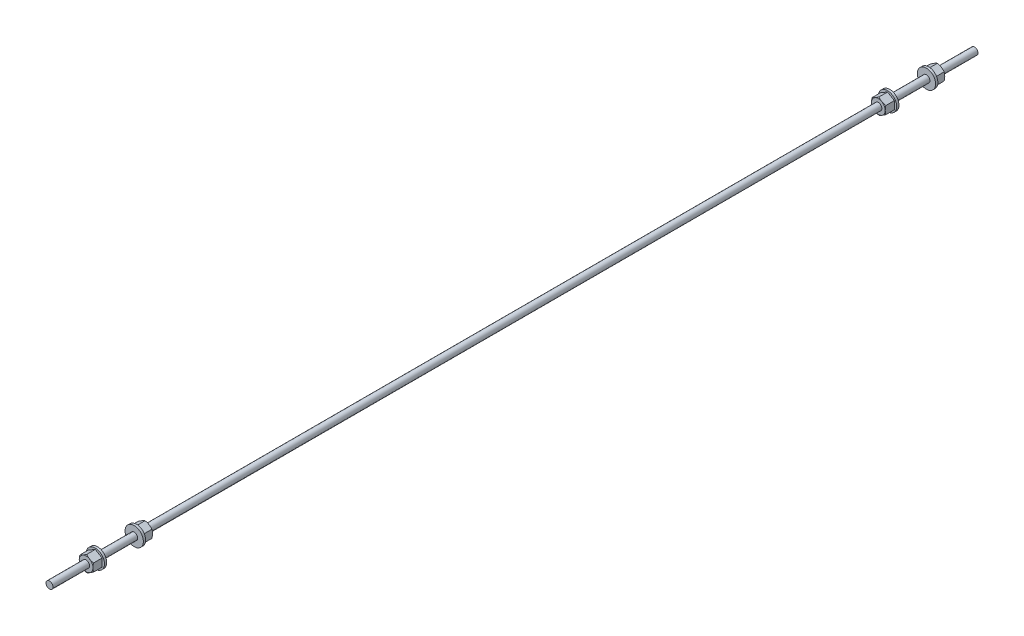
SolidWorks part; units mm, degrees
material "AISI 304"
ref_plane "Front Plane" through (0, 0, 0) normal (0, 0, 1) x (1, 0, 0)
ref_plane "Top Plane" through (0, 0, 0) normal (0, 1, 0) x (1, 0, 0)
ref_plane "Right Plane" through (0, 0, 0) normal (1, 0, 0) x (0, 0, -1)
sketch "Sketch1" plane through (0, 0, 0) normal (0, 0, 1) x (1, 0, 0)
  line L1 (0, 5.4993) -> (-4.7625, 2.7496)
  line L2 (-4.7625, 2.7496) -> (-4.7625, -2.7496)
  line L3 (-4.7625, -2.7496) -> (0, -5.4993)
  line L4 (0, -5.4993) -> (4.7625, -2.7496)
  line L5 (4.7625, -2.7496) -> (4.7625, 2.7496)
  line L6 (4.7625, 2.7496) -> (0, 5.4993)
  circle A0 centre (0, 0) radius 4.7625 construction
  dimension "Hex" = 9.525
extrude "Extrude1" add sketch "Sketch1" against normal blind 7.9375
sketch "Sketch13" plane through (0, 0, -7.9375) normal (0, 0, -1) x (-1, 0, 0)
  circle A0 centre (0, 0) radius 6.35
  dimension "Flange od" = 12.7
extrude "Extrude3" add sketch "Sketch13" against normal blind 1.5875
sketch "Sketch2" plane through (0, 0, 0) normal (0, 0, 1) x (1, 0, 0)
  circle A0 centre (0, 0) radius 4.7625 construction
  circle A1 centre (0, 0) radius 4.7625
extrude "Cut-Extrude1" cut sketch "Sketch2" against normal through all draft 60 flip side to cut
sketch "Sketch4" plane through (0, 0, 0) normal (0, 0, 1) x (1, 0, 0)
  circle A0 centre (0, 0) radius 2.413
  dimension "Thread Dia" = 4.826
sketch "Sketch14" plane through (0, 0, -7.9375) normal (0, 0, -1) x (-1, 0, 0)
  circle A0 centre (0, 0) radius 2.413
extrude "Boss-Extrude1" add sketch "Sketch14" along normal blind 12.7
ref_plane "Plane1" through (0, 0, -20.6375) normal (0, 0, -1) x (-1, 0, 0)
mirror "Mirror1" about plane through (0, 0, -20.6375) normal (0, 0, -1) of "Extrude3", "Cut-Extrude1", "Extrude1", "Boss-Extrude1"
sketch "Sketch15" plane through (0, 0, -41.275) normal (0, 0, -1) x (-1, 0, 0)
  circle A0 centre (0, 0) radius 2.413
extrude "Boss-Extrude2" add sketch "Sketch15" along normal blind 254
ref_plane "Plane2" through (0, 0, -295.275) normal (0, 0, -1) x (-1, 0, 0)
mirror "Mirror2" about plane through (0, 0, -295.275) normal (0, 0, -1) of "Extrude3", "Cut-Extrude1", "Extrude1", "Boss-Extrude1", "Mirror1", "Boss-Extrude2"
sketch "Sketch16" plane through (0, 0, -590.55) normal (0, 0, -1) x (-1, 0, 0)
  circle A0 centre (0, 0) radius 2.413
extrude "Boss-Extrude3" add sketch "Sketch16" along normal blind 25.4
extrude "Boss-Extrude4" add sketch "Sketch4" along normal blind 25.4
